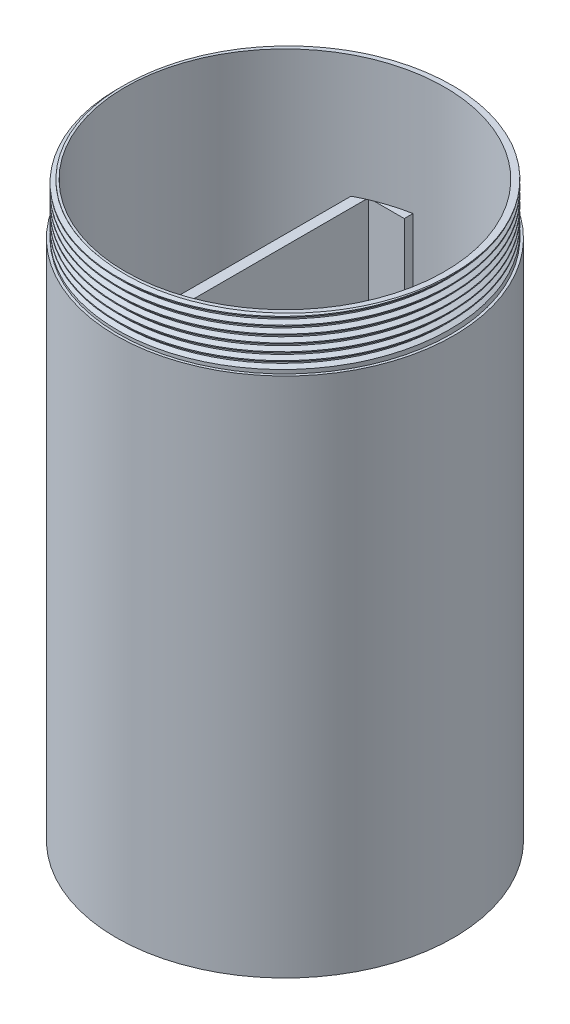
SolidWorks part; units mm, degrees
ref_plane "Front Plane" through (0, 0, 0) normal (0, 0, 1) x (1, 0, 0)
ref_plane "Top Plane" through (0, 0, 0) normal (0, 1, 0) x (1, 0, 0)
ref_plane "Right Plane" through (0, 0, 0) normal (1, 0, 0) x (0, 0, -1)
sketch "Sketch1" plane through (0, 0, 0) normal (0, 1, 0) x (1, 0, 0)
  circle A0 centre (0, 0) radius 33
  dimension "D1" = 66
extrude "Boss-Extrude1" add sketch "Sketch1" along normal blind 112
sketch "Sketch2" plane through (0, 112, 0) normal (0, 1, 0) x (1, 0, 0)
  circle A0 centre (0, 0) radius 31.25
  dimension "D1" = 62.5
extrude "Cut-Extrude1" cut sketch "Sketch2" against normal blind 107
sketch "Sketch3" plane through (0, 5, 0) normal (0, 1, 0) x (1, 0, 0)
  line L0 (0, 0) -> (0, 31.5) construction
  line L1 (0, 31.5) -> (0, -31.5) construction
  line L2 (0, 31.5) -> (0, -31.5)
  arc A0 (0, 31.5) -> (0, -31.5) centre (0, 0) ccw
extrude "Boss-Extrude2" add sketch "Sketch3" along normal blind 20
sketch "Sketch5" plane through (0, 112, 0) normal (0, 1, 0) x (1, 0, 0)
  circle A0 centre (0, 0) radius 32.5
  dimension "D1" = 65
sketch "Sketch6" plane through (0, 112, 0) normal (0, 1, 0) x (1, 0, 0)
  circle A0 centre (0, 0) radius 32.5
  circle A1 centre (0, 0) radius 33.3
  circle M2 centre (0, 0) radius 33
  dimension "D1" = 66.6
  dimension "D2" = 65
extrude "Cut-Extrude3" cut sketch "Sketch6" against normal blind 10 contours A0 M2 region at (-32.9067, 112, 0)
thread "Thread2" pitch 1.5 method cut profile "Thread Profile2" start angle 0, offset 2, length 11.05, pitch 1.5, diameter 65
ref_plane "Plane2" through (-32.5, 114, 0) normal (0, 0, 1) x (-1, 0, 0)
sketch "Thread Profile2" plane through (-32.5, 114, 0) normal (0, 0, 1) x (-1, 0, 0)
  line L0 (0, 0) -> (0, 1.5) construction
  line L11 (0, 0) -> (0, 1.3125)
  line L12 (0, 1.3125) -> (-0.8119, 0.8437)
  line L13 (-0.8119, 0.8437) -> (-0.8119, 0.4687)
  line L15 (-0.8119, 0.4687) -> (0, 0)
  line L17 (-0.8119, 0.6562) -> (0, 0.6562) construction
  point P2 (0, 0)
  dimension "Pitch" = 1.5
  dimension "Profile_Angle" = 60
  dimension "Profile_Land" = 0.375
  dimension "Profile_Height" = 0.8119
sketch "Sketch7" plane through (0, 0, 0) normal (0, -1, 0) x (1, 0, 0)
  line L0 (0, -32.5) -> (0, -33) construction
  line L1 (0, 32.5) -> (0, 33) construction
  line L2 (0, 33) -> (0, 32.5) construction
  line L3 (-5.6789, 32) -> (-5.6789, -32)
  arc A0 (-5.6789, 32) -> (-5.6789, -32) centre (0, 0) ccw
  circle A1 centre (0, 0) radius 33 construction
  circle A2 centre (0, 0) radius 32.5 construction
  dimension "D1" = 64
extrude "Boss-Extrude3" add sketch "Sketch7" against normal blind 63 from surface starting at face at (-15.625, 25, 0)
sketch "Sketch8" plane through (0, 88, 0) normal (0, 1, 0) x (1, 0, 0)
  line L0 (-12.6789, -28.9768) -> (-5.6789, -28.9768)
  line L1 (-5.6789, -30.7297) -> (-5.6789, 30.7297) construction
  line L2 (-5.6789, 29.0232) -> (-5.6789, -28.9768)
  line L4 (-5.6789, 29.0232) -> (-12.6789, 29.0232)
  line L5 (-12.6789, 29.0232) -> (-12.6789, -28.9768)
  dimension "D1" = 58
  dimension "D2" = 7
  dimension "D3" = 7
  dimension "D4" = 1.7064
extrude "Cut-Extrude4" cut sketch "Sketch8" against normal up to surface (63 mm away) up to face at (-2.8454, 25, 0)
sketch "Sketch12" plane through (0, 88, 0) normal (0, 1, 0) x (1, 0, 0)
  line L0 (-14.6789, 27.5879) -> (-14.6789, -27.5879)
  line L1 (-12.6789, 28.5623) -> (-12.6789, -28.5623) construction
  arc A0 (-12.6789, 28.5623) -> (-12.6789, -28.5623) centre (0, 0) ccw construction
  arc A1 (-14.6789, 27.5879) -> (-14.6789, -27.5879) centre (0, 0) ccw
  dimension "D1" = 2
extrude "Cut-Extrude5" cut sketch "Sketch12" against normal up to surface (83 mm away) contours A1 L0 up to face at (15.625, 5, 0)
sketch "Sketch13" plane through (0, 0, 0) normal (1, 0, 0) x (0, 0, -1)
  line L0 (-31.25, 25) -> (31.25, 25) construction
  line L1 (-13, 25) -> (13, 25)
  line L2 (-13, 25) -> (-13, 5)
  line L3 (-13, 5) -> (13, 5)
  line L4 (13, 25) -> (13, 5)
  line L5 (31.25, 5) -> (-31.25, 5) construction
  line L6 (-33, 102) -> (-33, 0) construction
  line L7 (33, 0) -> (33, 102) construction
  point P6 (17.3521, 5)
  dimension "D1" = 20
  dimension "D2" = 20
extrude "Cut-Extrude6" cut sketch "Sketch13" against normal blind 21
sketch "Sketch16" plane through (0, 25, 0) normal (0, 1, 0) x (1, 0, 0)
  line L0 (-31.7307, -24.9513) -> (42.6024, -24.9513) construction
  line L1 (5.4358, -24.9513) -> (5.4358, 3.0487) construction
  line L2 (1.9358, 3.0487) -> (8.9358, 3.0487)
  line L4 (8.9358, 3.0487) -> (8.9358, 10.0487)
  line L5 (1.9358, 10.0487) -> (8.9358, 10.0487)
  line L6 (1.9358, 3.0487) -> (1.9358, 10.0487)
  line L7 (5.4358, 10.0487) -> (5.4358, 36.5891) construction
  point P5 (5.4358, 3.0487)
  dimension "D1" = 28
  dimension "D2" = 3.5
  dimension "D3" = 7
extrude "Cut-Extrude8" cut sketch "Sketch16" against normal blind 50
sketch "Sketch20" plane through (0, 25, 0) normal (0, 1, 0) x (1, 0, 0)
  line L0 (-2.6789, 26.8255) -> (0, 26.8255)
  line L1 (-12.6789, 28.5623) -> (-12.6789, -28.5623) construction
  line L2 (0, 13) -> (0, 31.25) construction
  line L3 (0, 26.8255) -> (0, 13)
  line L4 (0, 31.25) -> (0, 13) construction
  line L5 (0, 13) -> (-12.6789, 13)
  line L6 (-12.6789, 13) -> (-12.6789, 16.8255)
  line L7 (-37.1965, 0) -> (37.1965, 0) construction
  line L8 (0, -13) -> (-12.6789, -13)
  line L9 (0, -26.8255) -> (0, -13)
  line L10 (-2.6789, -26.8255) -> (0, -26.8255)
  line L11 (-12.6789, -13) -> (-12.6789, -16.8255)
  arc A0 (-2.6789, 26.8255) -> (-12.6789, 16.8255) centre (-2.6789, 16.8255) ccw
  arc A1 (-2.6789, -26.8255) -> (-12.6789, -16.8255) centre (-2.6789, -16.8255) cw
  point P13 (-12.6789, 26.8255)
  dimension "D1" = 10
extrude "Cut-Extrude10" cut sketch "Sketch20" against normal up to surface (20 mm away) up to face at (5.4358, 5, -6.5487)
